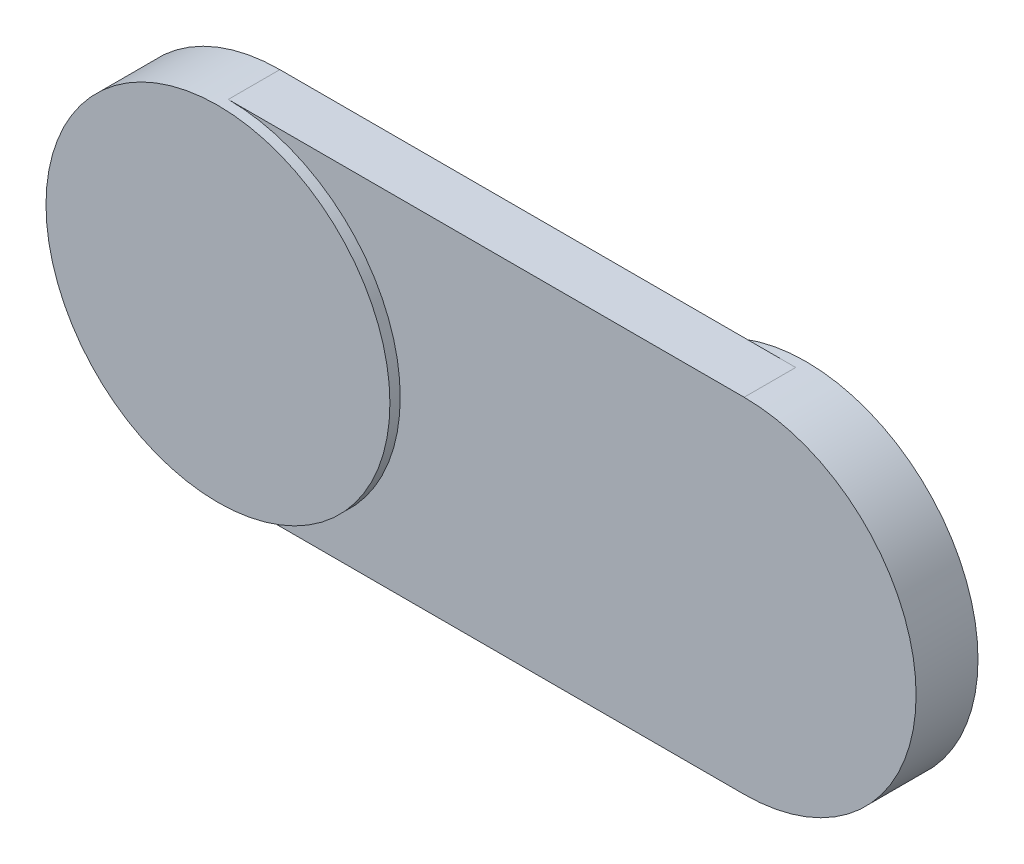
SolidWorks part; units mm, degrees
ref_plane "前视基准面" through (0, 0, 0) normal (0, 0, 1) x (1, 0, 0)
ref_plane "上视基准面" through (0, 0, 0) normal (0, 1, 0) x (1, 0, 0)
ref_plane "右视基准面" through (0, 0, 0) normal (1, 0, 0) x (0, 0, -1)
sketch "草图1" plane through (0, 0, 0) normal (0, 0, 1) x (1, 0, 0)
  line L0 (0, 50) -> (-150, 50)
  line L5 (0, 0) -> (-150, 0)
  line L6 (0, 0) -> (0, 100)
  line L7 (0, 100) -> (-150, 100)
  line L8 (-150, 0) -> (-150, 100)
  circle A6 centre (0, 50) radius 50
  circle A7 centre (0, 50) radius 25
  circle A8 centre (-150, 50) radius 50
  circle A9 centre (-150, 50) radius 25
  circle A10 centre (-75, 50) radius 5
  dimension "D1" = 100
  dimension "D2" = 150
  dimension "D3" = 50
  dimension "D4" = 50
  dimension "D5" = 10
extrude "凸台-拉伸1" add sketch "草图1" along normal blind 15 contours L7 L8 L5 L6
extrude "凸台-拉伸4" add sketch "草图1<10>" along normal blind 15 contours A7 L6 A6 | L6 A7 | L8 A9 | A9 L8 A8 region at (-151.118, 87.5, 0) region at (-160.6103, 50, 0) region at (34.5648, 84.5648, 0) region at (10.6103, 50, 0)
sketch "草图1<10>" plane through (0, 0, 0) normal (0, 0, 1) x (1, 0, 0) same geometry as "草图1"
extrude "凸台-拉伸6" add sketch "草图1<14>" along normal blind 18 contours A9 L0 A8 L8 | A9 L8 A8 | A9 L8 A8 L0 | L8 A9 L0 | L0 A9 L8 | L8 A9 region at (-125.2426, 25.2426, 0) region at (-125.2426, 74.7574, 0) region at (-139.3897, 39.3897, 0) region at (-139.3897, 60.6103, 0) region at (-151.118, 87.5, 0) region at (-160.6103, 50, 0)
sketch "草图1<14>" plane through (0, 0, 0) normal (0, 0, 1) x (1, 0, 0) same geometry as "草图1"
extrude "凸台-拉伸7" add sketch "草图1<16>" against normal blind 3 contours A7 L6 A6 | A7 L0 A6 L6 | A7 L6 A6 L0 | L6 A7 L0 | L0 A7 L6 | L6 A7 region at (34.5648, 84.5648, 0) region at (-24.7574, 74.7574, 0) region at (-24.7574, 25.2426, 0) region at (10.6103, 50, 0) region at (-10.6103, 60.6103, 0) region at (-10.6103, 39.3897, 0)
sketch "草图1<16>" plane through (0, 0, 0) normal (0, 0, 1) x (1, 0, 0) same geometry as "草图1"
extrude "凸台-拉伸8" add sketch "草图1<17>" against normal blind 25 contours A10
sketch "草图1<17>" plane through (0, 0, 0) normal (0, 0, 1) x (1, 0, 0) same geometry as "草图1"
